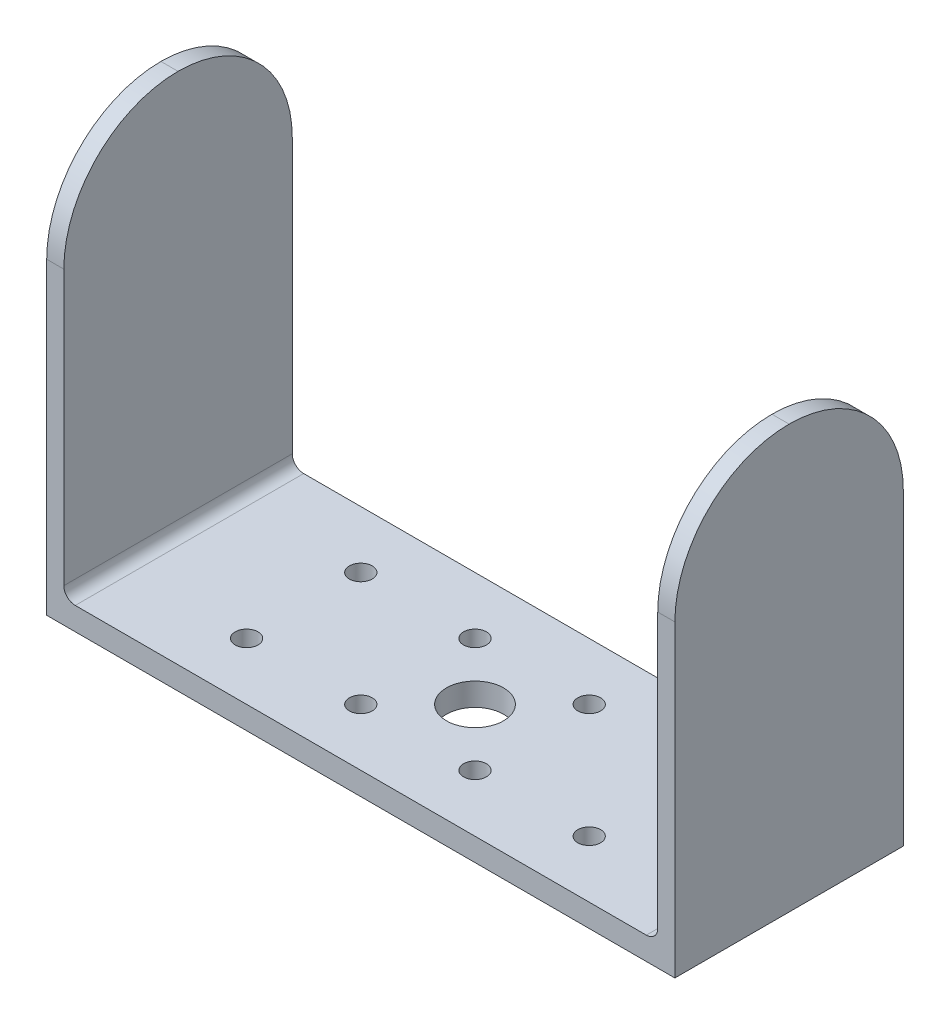
SolidWorks part; units mm, degrees
ref_plane "前视基准面" through (0, 0, 0) normal (0, 0, 1) x (1, 0, 0)
ref_plane "上视基准面" through (0, 0, 0) normal (0, 1, 0) x (1, 0, 0)
ref_plane "右视基准面" through (0, 0, 0) normal (1, 0, 0) x (0, 0, -1)
other "Configuration Table"
sketch "草图1" plane through (0, 0, 0) normal (0, 1, 0) x (1, 0, 0)
  line L1 (-27.5, 10) -> (27.5, 10)
  line L2 (-27.5, 10) -> (-27.5, -10)
  line L3 (-27.5, -10) -> (27.5, -10)
  line L4 (27.5, 10) -> (27.5, -10)
  line L5 (0, -10) -> (0, 10) construction
  line L6 (-27.5, 0) -> (27.5, 0) construction
  point P0 (0, 0)
  dimension "D1" = 55
  dimension "D2" = 20
extrude "凸台-拉伸1" add sketch "草图1" against normal blind 2
sketch "草图3" plane through (0, 0, 0) normal (0, 1, 0) x (1, 0, 0)
  line L0 (-27.5, -10) -> (27.5, -10) construction
  line L1 (-27.5, 10) -> (-26, 10)
  line L2 (-27.5, 10) -> (-27.5, -10)
  line L3 (-27.5, -10) -> (-26, -10)
  line L4 (-26, 10) -> (-26, -10)
  line L5 (0, 0) -> (0, 17.4213) construction
  line L6 (27.5, -10) -> (26, -10)
  line L7 (26, 10) -> (26, -10)
  line L8 (27.5, 10) -> (26, 10)
  line L9 (27.5, 10) -> (27.5, -10)
extrude "凸台-拉伸2" add sketch "草图3" along normal blind 35
sketch "草图4" plane through (-27.5, 0, 0) normal (-1, 0, 0) x (0, 0, 1)
  line L0 (0, 35) -> (0, -4.5541) construction
  line L1 (-10, 35) -> (10, 35) construction
  line L2 (0, 35) -> (0, 32) construction
  circle A0 centre (0, 25.4811) radius 6.5189
fillet "圆角1" radius 10 4 edges at (-26.75, 35, -10) (-26.75, 35, 10) (26.75, 35, 10) (26.75, 35, -10)
fillet "圆角3" radius 1 2 edges at (-26, 0, 0) (26, 0, 0)
sketch "草图6" plane through (0, -2, 0) normal (0, -1, 0) x (1, 0, 0)
  line L0 (5, 5) -> (15, 5) construction
  line L5 (0, 50.7241) -> (0, -50.7241) construction
  line L6 (65, 0) -> (-65, 0) construction
  line L7 (-5, 5) -> (5, 5) construction
  line L8 (-5, 5) -> (-5, -5) construction
  line L9 (-5, -5) -> (5, -5) construction
  line L10 (5, 5) -> (5, -5) construction
  line L11 (0, -5) -> (0, 5) construction
  line L12 (-5, 0) -> (5, 0) construction
  circle A0 centre (0, 0) radius 2.5
  circle A1 centre (-5, 5) radius 1
  circle A2 centre (-5, -5) radius 1
  circle A3 centre (5, -5) radius 1
  circle A4 centre (5, 5) radius 1
  circle A5 centre (15, 5) radius 1
  circle A6 centre (-15, 5) radius 1
  circle A7 centre (15, -5) radius 1
  circle A8 centre (-15, -5) radius 1
  point P0 (0, 0)
  dimension "D1" = 5
  dimension "D2" = 5
extrude "切除-拉伸1" cut sketch "草图6" against normal up to next
